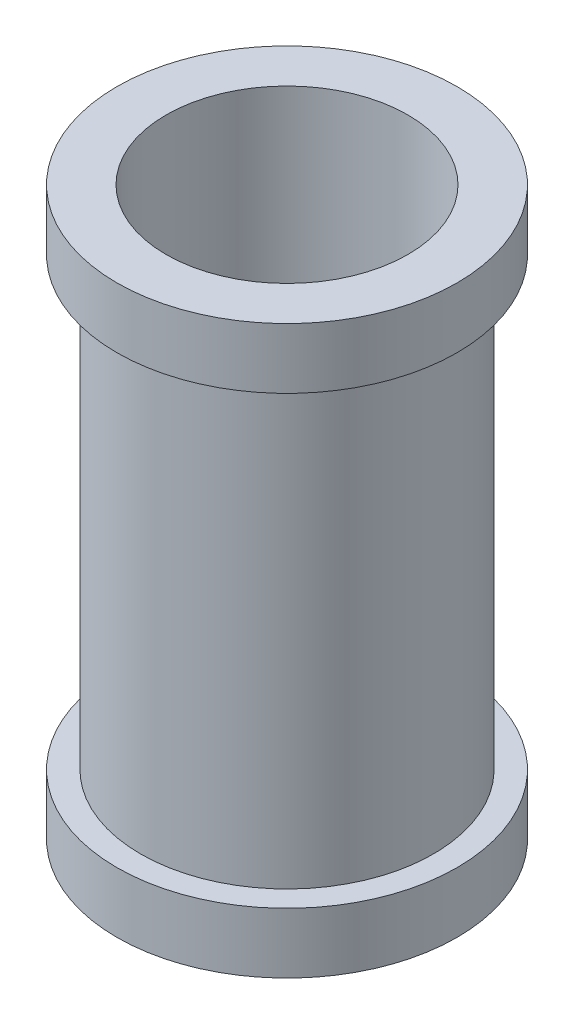
SolidWorks part; units mm, degrees
ref_plane "Front Plane" through (0, 0, 0) normal (0, 0, 1) x (1, 0, 0)
ref_plane "Top Plane" through (0, 0, 0) normal (0, 1, 0) x (1, 0, 0)
ref_plane "Right Plane" through (0, 0, 0) normal (1, 0, 0) x (0, 0, -1)
sketch "Sketch3" plane through (0, 0, 0) normal (0, 0, 1) x (1, 0, 0)
  line L0 (0, 0) -> (8.255, 0)
  line L1 (8.255, 0) -> (8.255, 10.16)
  line L2 (8.255, 10.16) -> (4.2862, 10.16)
  line L3 (4.2862, 10.16) -> (4.2862, 85.09)
  line L4 (8.255, 85.09) -> (4.2862, 85.09)
  line L5 (8.255, 85.09) -> (8.255, 95.25)
  line L6 (8.255, 95.25) -> (0, 95.25)
  line L7 (0, 95.25) -> (0, 0)
  line L9 (-20.32, 95.25) -> (-20.32, 0) construction
  dimension "D1" = 8.255
revolve "Revolve1" add sketch "Sketch3" angle 360 about L9
sketch "Sketch5" plane through (0, 0, 0) normal (0, -1, 0) x (1, 0, 0)
  line L0 (-48.895, 0) -> (8.255, 0) construction
  circle A0 centre (-20.32, 0) radius 28.575 construction
  point P5 (-20.32, 0)
